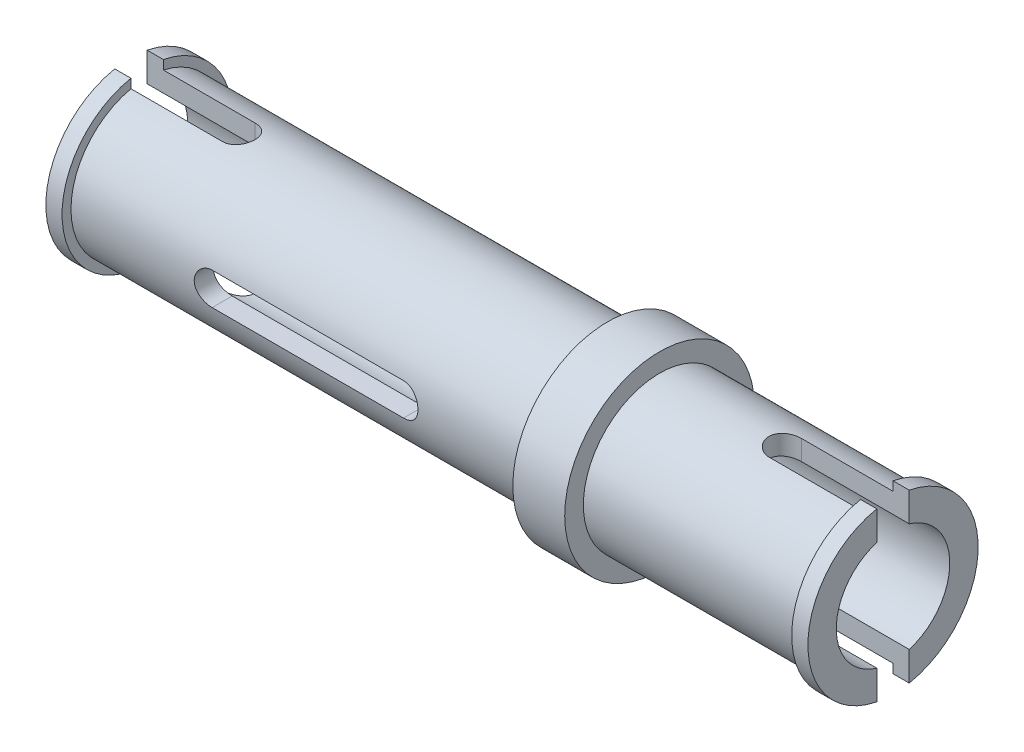
SolidWorks part; units mm, degrees
ref_plane "Front Plane" through (0, 0, 0) normal (0, 0, 1) x (1, 0, 0)
ref_plane "Top Plane" through (0, 0, 0) normal (0, 1, 0) x (1, 0, 0)
ref_plane "Right Plane" through (0, 0, 0) normal (1, 0, 0) x (0, 0, -1)
sketch "Sketch1" plane through (0, 0, 0) normal (1, 0, 0) x (0, 0, -1)
  circle A0 centre (0, 0) radius 1.75
  circle A1 centre (0, 0) radius 2.925
  dimension "D1" = 3.5
  dimension "D2" = 5.85
extrude "Middle Ring" add sketch "Sketch1" along normal mid plane 1.6
sketch "Sketch2" plane through (0, 0, 0) normal (1, 0, 0) x (0, 0, -1)
  circle A0 centre (0, 0) radius 1.75 construction
  circle A1 centre (0, 0) radius 1.75
  circle A2 centre (0, 0) radius 2.35
  dimension "D1" = 4.7
extrude "Outer Body" add sketch "Sketch2" along normal blind 7.5 and the other way blind 15
sketch "Sketch3" plane through (7.5, 0, 0) normal (1, 0, 0) x (0, 0, -1)
  circle A0 centre (0, 0) radius 1.75 construction
  circle A1 centre (0, 0) radius 1.75
  circle A2 centre (0, 0) radius 2.625
  dimension "D1" = 5.25
extrude "Outer Rim" add sketch "Sketch3" along normal blind 0.5
sketch "Sketch6" plane through (-15, 0, 0) normal (-1, 0, 0) x (0, 0, 1)
  circle A0 centre (0, 0) radius 1.75 construction
  circle A1 centre (0, 0) radius 1.75
  circle A2 centre (0, 0) radius 2.625 construction
  circle A3 centre (0, 0) radius 2.625
extrude "Outer Rim 2" add sketch "Sketch6" along normal blind 0.5
sketch "Sketch4" plane through (0, 0, 0) normal (0, 0, 1) x (1, 0, 0)
  line L0 (-4.8, 0) -> (-10.7, 0) construction
  line L1 (-4.8, -0.5) -> (-10.7, -0.5)
  line L2 (-4.8, 0.5) -> (-10.7, 0.5)
  line L3 (-15.5, 2.625) -> (-15.5, -2.625) construction
  arc A0 (-4.8, -0.5) -> (-4.8, 0.5) centre (-4.8, 0) ccw
  arc A1 (-10.7, 0.5) -> (-10.7, -0.5) centre (-10.7, 0) ccw
  point P2 (-7.75, 0)
  point P8 (0, 0)
  point P9 (0, 0)
  point P10 (-9.0938, 0)
  point P11 (0, 0)
  point P13 (-7.4941, 0)
  dimension "D2" = 6.9
  dimension "D1" = 1
  dimension "D3" = 4.3
extrude "Middle Slot " cut sketch "Sketch4" against normal through all both and the other way through all
sketch "Sketch5" plane through (0, 0, 0) normal (0, 1, 0) x (1, 0, 0)
  line L0 (11.325, 0) -> (4.675, 0) construction
  line L1 (8, -2.625) -> (8, 2.625) construction
  line L2 (11.325, -0.5) -> (4.675, -0.5)
  line L3 (11.325, 0.5) -> (4.675, 0.5)
  line L4 (-3.75, 0.2665) -> (-3.75, 3.8777) construction
  line L5 (-18.825, 0) -> (-12.175, 0) construction
  line L6 (-18.825, -0.5) -> (-12.175, -0.5)
  line L7 (-18.825, 0.5) -> (-12.175, 0.5)
  line L8 (-15.5, 2.625) -> (-15.5, -2.625) construction
  arc A0 (11.325, -0.5) -> (11.325, 0.5) centre (11.325, 0) ccw
  arc A1 (4.675, 0.5) -> (4.675, -0.5) centre (4.675, 0) ccw
  arc A2 (-18.825, -0.5) -> (-18.825, 0.5) centre (-18.825, 0) cw
  arc A3 (-12.175, 0.5) -> (-12.175, -0.5) centre (-12.175, 0) cw
  point P4 (-15.5, 0)
  point P5 (8, 0)
  point P14 (-15.5, 0)
  point P21 (-3.75, 0.2665)
  dimension "D2" = 15.85
  dimension "D1" = 1
  dimension "D3" = 3.825
extrude "End Slots" cut sketch "Sketch5" against normal through all both and the other way through all
